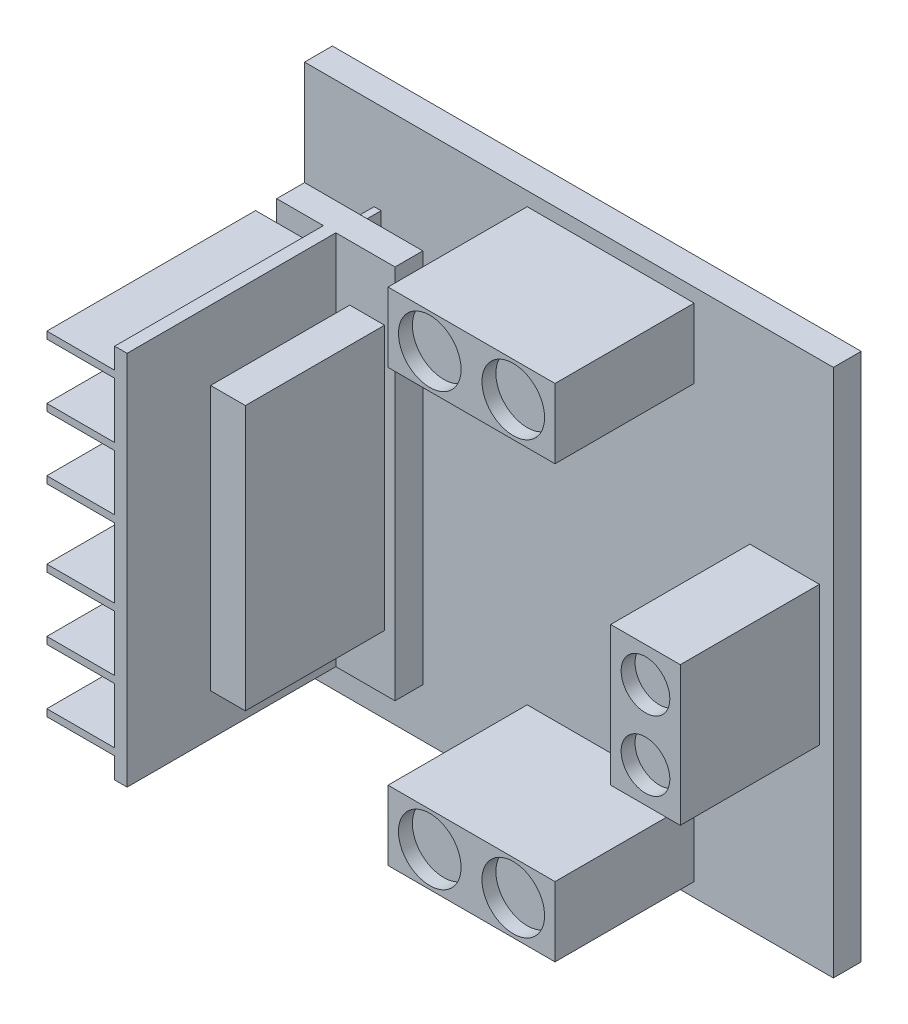
SolidWorks part; units mm, degrees
ref_plane "Front Plane" through (0, 0, 0) normal (0, 0, 1) x (1, 0, 0)
ref_plane "Top Plane" through (0, 0, 0) normal (0, 1, 0) x (1, 0, 0)
ref_plane "Right Plane" through (0, 0, 0) normal (1, 0, 0) x (0, 0, -1)
sketch "Sketch1" plane through (0, 0, 0) normal (0, 0, 1) x (1, 0, 0)
  line L0 (-20.2922, -144.6327) -> (-11.9422, -144.6327) construction
  line L1 (18.4712, -106.6327) -> (56.4712, -106.6327)
  line L2 (18.4712, -106.6327) -> (18.4712, -144.6327)
  line L3 (18.4712, -144.6327) -> (56.4712, -144.6327)
  line L4 (56.4712, -106.6327) -> (56.4712, -144.6327)
  dimension "D1" = 38
  dimension "D2" = 38
  dimension "D3" = 0
extrude "Boss-Extrude1" add sketch "Sketch1" along normal blind 2
sketch "Sketch2" plane through (0, 0, 2) normal (0, 0, 1) x (1, 0, 0)
  line L0 (18.4712, -125.6327) -> (56.4712, -125.6327) construction
  line L1 (23.4712, -113.1327) -> (23.9712, -113.1327)
  line L2 (23.4712, -113.1327) -> (23.4712, -138.1327)
  line L3 (23.4712, -138.1327) -> (23.9712, -138.1327)
  line L4 (23.9712, -113.1327) -> (23.9712, -138.1327)
  line L5 (18.4712, -106.6327) -> (18.4712, -144.6327) construction
  line L6 (56.4712, -144.6327) -> (56.4712, -106.6327) construction
  dimension "D1" = 0.5
  dimension "D2" = 25
  dimension "D3" = 12.5
  dimension "D4" = 5
extrude "Boss-Extrude2" add sketch "Sketch2" along normal blind 2
sketch "Sketch4" plane through (0, 0, 4) normal (0, 0, 1) x (1, 0, 0)
  line L0 (23.9712, -138.1327) -> (23.9712, -113.1327) construction
  line L1 (20.4712, -112.1327) -> (28.9712, -112.1327)
  line L2 (20.4712, -112.1327) -> (20.4712, -139.1327)
  line L3 (20.4712, -139.1327) -> (28.9712, -139.1327)
  line L4 (28.9712, -112.1327) -> (28.9712, -139.1327)
  line L5 (23.4712, -113.1327) -> (23.4712, -138.1327) construction
  line L6 (23.9712, -113.1327) -> (23.4712, -113.1327) construction
  line L7 (23.4712, -138.1327) -> (23.9712, -138.1327) construction
  dimension "D1" = 5
  dimension "D2" = 3
  dimension "D3" = 1
  dimension "D4" = 1
extrude "Boss-Extrude3" add sketch "Sketch4" along normal blind 2
sketch "Sketch5" plane through (0, 0, 6) normal (0, 0, 1) x (1, 0, 0)
  line L0 (20.4712, -125.6327) -> (28.9712, -125.6327) construction
  line L1 (18.9526, -113.6327) -> (24.3791, -113.6327)
  line L2 (18.9526, -113.6327) -> (18.9526, -114.1327)
  line L3 (18.9526, -114.1327) -> (24.3791, -114.1327)
  line L4 (24.3791, -113.6327) -> (24.3791, -114.1327)
  line L5 (18.9526, -118.1327) -> (24.3791, -118.1327)
  line L6 (18.9526, -118.1327) -> (18.9526, -118.6327)
  line L7 (18.9526, -118.6327) -> (24.3791, -118.6327)
  line L8 (24.3791, -118.1327) -> (24.3791, -118.6327)
  line L9 (18.9526, -122.6327) -> (24.3791, -122.6327)
  line L10 (18.9526, -122.6327) -> (18.9526, -123.1327)
  line L11 (18.9526, -123.1327) -> (24.3791, -123.1327)
  line L12 (24.3791, -122.6327) -> (24.3791, -123.1327)
  line L13 (20.4712, -112.1327) -> (20.4712, -139.1327) construction
  line L14 (28.9712, -139.1327) -> (28.9712, -112.1327) construction
  line L15 (24.3791, -128.6327) -> (24.3791, -128.1327)
  line L16 (18.9526, -128.1327) -> (24.3791, -128.1327)
  line L17 (18.9526, -128.6327) -> (18.9526, -128.1327)
  line L18 (18.9526, -128.6327) -> (24.3791, -128.6327)
  line L19 (24.3791, -133.1327) -> (24.3791, -132.6327)
  line L20 (18.9526, -132.6327) -> (24.3791, -132.6327)
  line L21 (18.9526, -133.1327) -> (18.9526, -132.6327)
  line L22 (18.9526, -133.1327) -> (24.3791, -133.1327)
  line L23 (24.3791, -137.6327) -> (24.3791, -137.1327)
  line L24 (18.9526, -137.1327) -> (24.3791, -137.1327)
  line L25 (18.9526, -137.6327) -> (18.9526, -137.1327)
  line L26 (18.9526, -137.6327) -> (24.3791, -137.6327)
  dimension "D1" = 0.5
  dimension "D2" = 0.5
  dimension "D3" = 0.5
  dimension "D4" = 2.5
  dimension "D5" = 4
  dimension "D6" = 4
extrude "Boss-Extrude4" add sketch "Sketch5" along normal blind 15
sketch "Sketch6" plane through (0, 0, 6) normal (0, 0, 1) x (1, 0, 0)
  line L0 (28.9712, -112.1327) -> (20.4712, -112.1327) construction
  line L1 (23.8288, -112.1327) -> (24.7212, -112.1327)
  line L2 (23.8288, -112.1327) -> (23.8288, -139.1327)
  line L3 (23.8288, -139.1327) -> (24.7212, -139.1327)
  line L4 (24.7212, -112.1327) -> (24.7212, -139.1327)
  line L5 (20.4712, -139.1327) -> (28.9712, -139.1327) construction
extrude "Boss-Extrude5" add sketch "Sketch6" along normal up to surface (15 mm away) up to face at (21.6658, -113.8827, 21)
sketch "Sketch7" plane through (0, 0, 6) normal (0, 0, 1) x (1, 0, 0)
  line L1 (25.7212, -116.1327) -> (28.2212, -116.1327)
  line L2 (25.7212, -116.1327) -> (25.7212, -135.1327)
  line L3 (25.7212, -135.1327) -> (28.2212, -135.1327)
  line L4 (28.2212, -116.1327) -> (28.2212, -135.1327)
  line L5 (18.9526, -114.1327) -> (23.8288, -114.1327) construction
  line L6 (23.8288, -137.1327) -> (18.9526, -137.1327) construction
  line L7 (24.7212, -139.1327) -> (24.7212, -112.1327) construction
  dimension "D1" = 2.5
  dimension "D2" = 2
  dimension "D3" = 2
  dimension "D4" = 1
extrude "Boss-Extrude6" add sketch "Sketch7" along normal blind 10
sketch "Sketch8" plane through (0, 0, 2) normal (0, 0, 1) x (1, 0, 0)
  line L0 (56.4712, -144.6327) -> (56.4712, -106.6327) construction
  line L1 (34.4712, -107.6327) -> (46.4712, -107.6327)
  line L2 (34.4712, -107.6327) -> (34.4712, -112.6327)
  line L3 (34.4712, -112.6327) -> (46.4712, -112.6327)
  line L4 (46.4712, -107.6327) -> (46.4712, -112.6327)
  line L5 (34.4712, -138.6327) -> (46.4712, -138.6327)
  line L6 (34.4712, -138.6327) -> (34.4712, -143.6327)
  line L7 (34.4712, -143.6327) -> (46.4712, -143.6327)
  line L8 (46.4712, -138.6327) -> (46.4712, -143.6327)
  line L9 (50.4712, -120.6327) -> (55.4712, -120.6327)
  line L10 (50.4712, -120.6327) -> (50.4712, -130.6327)
  line L11 (50.4712, -130.6327) -> (55.4712, -130.6327)
  line L12 (55.4712, -120.6327) -> (55.4712, -130.6327)
  line L13 (18.4712, -125.6327) -> (56.4712, -125.6327) construction
  line L14 (18.4712, -106.6327) -> (18.4712, -144.6327) construction
  line L15 (56.4712, -106.6327) -> (18.4712, -106.6327) construction
  line L16 (18.4712, -144.6327) -> (56.4712, -144.6327) construction
  dimension "D1" = 5
  dimension "D2" = 1
  dimension "D3" = 5
  dimension "D4" = 10
  dimension "D5" = 12
  dimension "D6" = 10
  dimension "D7" = 10
  dimension "D8" = 12
  dimension "D9" = 5
  dimension "D10" = 5
  dimension "D11" = 1
  dimension "D12" = 1
extrude "Boss-Extrude7" add sketch "Sketch8" along normal blind 10
sketch "Sketch9" plane through (0, 0, 12) normal (0, 0, 1) x (1, 0, 0)
  line L0 (34.4712, -107.6327) -> (34.4712, -112.6327) construction
  line L1 (46.4712, -112.6327) -> (46.4712, -107.6327) construction
  line L2 (55.4712, -120.6327) -> (50.4712, -120.6327) construction
  line L3 (18.4712, -125.6327) -> (56.4712, -125.6327) construction
  line L4 (18.4712, -106.6327) -> (18.4712, -144.6327) construction
  line L5 (56.4712, -144.6327) -> (56.4712, -106.6327) construction
  circle A0 centre (37.4712, -110.1327) radius 2.25
  circle A1 centre (43.4712, -110.1327) radius 2.25
  circle A2 centre (52.9712, -123.1327) radius 1.75
  circle A3 centre (52.9712, -128.1327) radius 1.75
  circle A4 centre (43.4712, -141.1327) radius 2.25
  circle A5 centre (37.4712, -141.1327) radius 2.25
  dimension "D1" = 4.5
  dimension "D2" = 4.5
  dimension "D3" = 3
  dimension "D4" = 3
  dimension "D5" = 3.5
  dimension "D6" = 2.5
extrude "Cut-Extrude1" cut sketch "Sketch9" against normal blind 1
